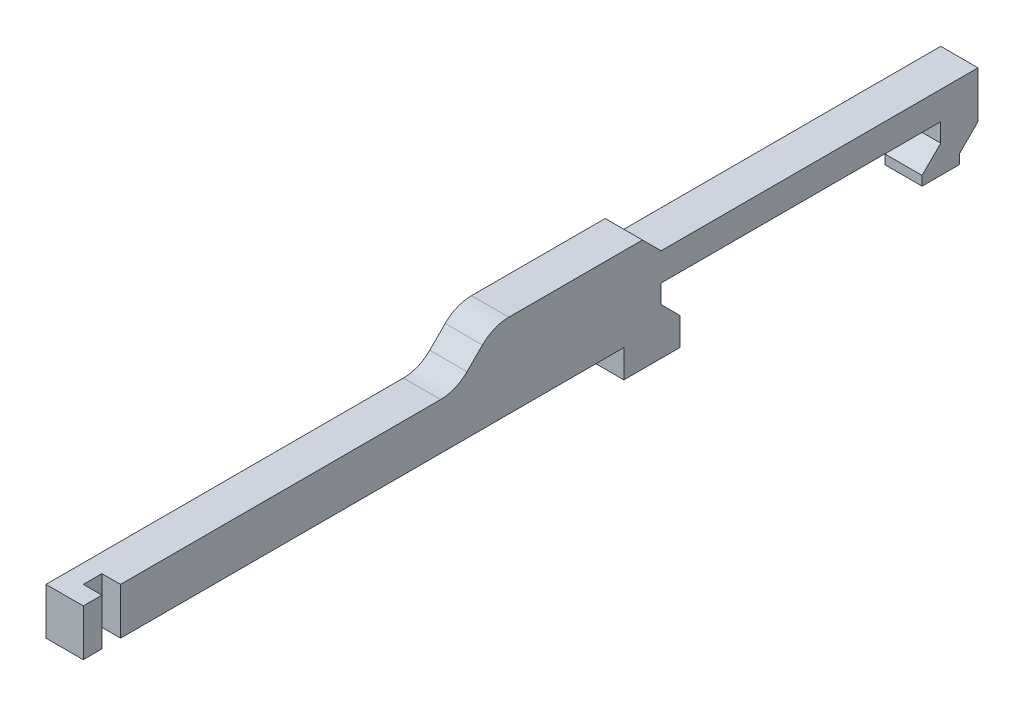
SolidWorks part; units mm, degrees
ref_plane "Спереди" through (0, 0, 0) normal (0, 0, 1) x (1, 0, 0)
ref_plane "Сверху" through (0, 0, 0) normal (0, 1, 0) x (1, 0, 0)
ref_plane "Справа" through (0, 0, 0) normal (1, 0, 0) x (0, 0, -1)
sketch "Эскиз1" plane through (0, 0, 0) normal (1, 0, 0) x (0, 0, -1)
  line L0 (20, 2.5) -> (22, 4.5)
  line L1 (0, 0) -> (20, 0)
  line L2 (0, 0) -> (0, 2.5)
  line L3 (0, 2.5) -> (20, 2.5)
  line L4 (20, 0) -> (20, 2.5)
  line L5 (22, 4.5) -> (22, 2.5) construction
  line L6 (22, 2.5) -> (20, 2.5) construction
  line L7 (22, 4.5) -> (29, 4.5)
  line L8 (20, 0) -> (29, 0)
  line L9 (29, 0) -> (29, -1.5)
  line L10 (29, -1.5) -> (32, -1.5)
  line L11 (32, -1.5) -> (32, 0)
  line L12 (32, 0) -> (31, 1)
  line L13 (31, 1) -> (31, 2)
  line L14 (31, 2) -> (46, 2)
  line L15 (32, 0) -> (31, 0) construction
  line L16 (31, 0) -> (31, 1) construction
  line L17 (38.5, 2) -> (38.5, 1) construction
  line L18 (45, 0) -> (46, 1)
  line L19 (46, 1) -> (46, 2)
  line L20 (45, 0) -> (45, -0.5)
  line L21 (45, -0.5) -> (47, -0.5)
  line L22 (47, -0.5) -> (47, 0)
  line L23 (47, 0) -> (48, 1)
  line L24 (48, 1) -> (48, 4.5)
  line L25 (48, 4.5) -> (29, 4.5)
  dimension "D1" = 2.5
  dimension "D2" = 20
  dimension "D3" = 2
  dimension "D4" = 2
  dimension "D5" = 7
  dimension "D6" = 9
  dimension "D7" = 1.5
  dimension "D8" = 3
  dimension "D9" = 1.5
  dimension "D10" = 1
  dimension "D11" = 1
  dimension "D12" = 1
  dimension "D13" = 15
  dimension "D14" = 0.5
  dimension "D15" = 2
extrude "Бобышка-Вытянуть1" add sketch "Эскиз1" along normal blind 2 contours L24 L25 L7 L0 L4 L8 L9 L10 L11 L12 L13 L14 L19 L18 L20 L21 L22 L23 | L1 L4 L3 L2 region at (0, 1.25, -10) region at (0, 2.4238, -32.8558)
fillet "Скругление1" radius 2 2 edges at (1, 4.5, -22) (1, 2.5, -20)
sketch "Эскиз2" plane through (0, 2.5, 0) normal (0, 1, 0) x (1, 0, 0)
  line L0 (2, 0) -> (2, 1) construction
  line L1 (2, 0) -> (2, 19.1716) construction
  line L3 (2, 1) -> (1, 1)
  line L4 (2, 1) -> (2, 2)
  line L5 (2, 2) -> (1, 2)
  line L6 (1, 1) -> (1, 2)
  dimension "D1" = 1
  dimension "D2" = 1
  dimension "D3" = 1
extrude "Вырез-Вытянуть1" cut sketch "Эскиз2" against normal through all
sketch "Эскиз3" plane through (2, 0, 0) normal (1, 0, 0) x (0, 0, -1)
  line L0 (48, 4.5) -> (48, 3.5)
  line L1 (48, 1) -> (48, 4.5) construction
  line L2 (48, 3.5) -> (31, 3.5)
  line L3 (48, 4.5) -> (31, 4.5)
  line L4 (48, 4.5) -> (22.8284, 4.5) construction
  line L5 (31, 4.5) -> (30, 4.5)
  line L6 (30, 4.5) -> (31, 3.5)
  line L7 (31, 4.5) -> (31, 3.5) construction
  line L8 (31, 3.5) -> (31, 2) construction
  line L9 (31, 1) -> (31, 2) construction
  dimension "D1" = 1
  dimension "D2" = 1
extrude "Вырез-Вытянуть2" cut sketch "Эскиз3" against normal through all
